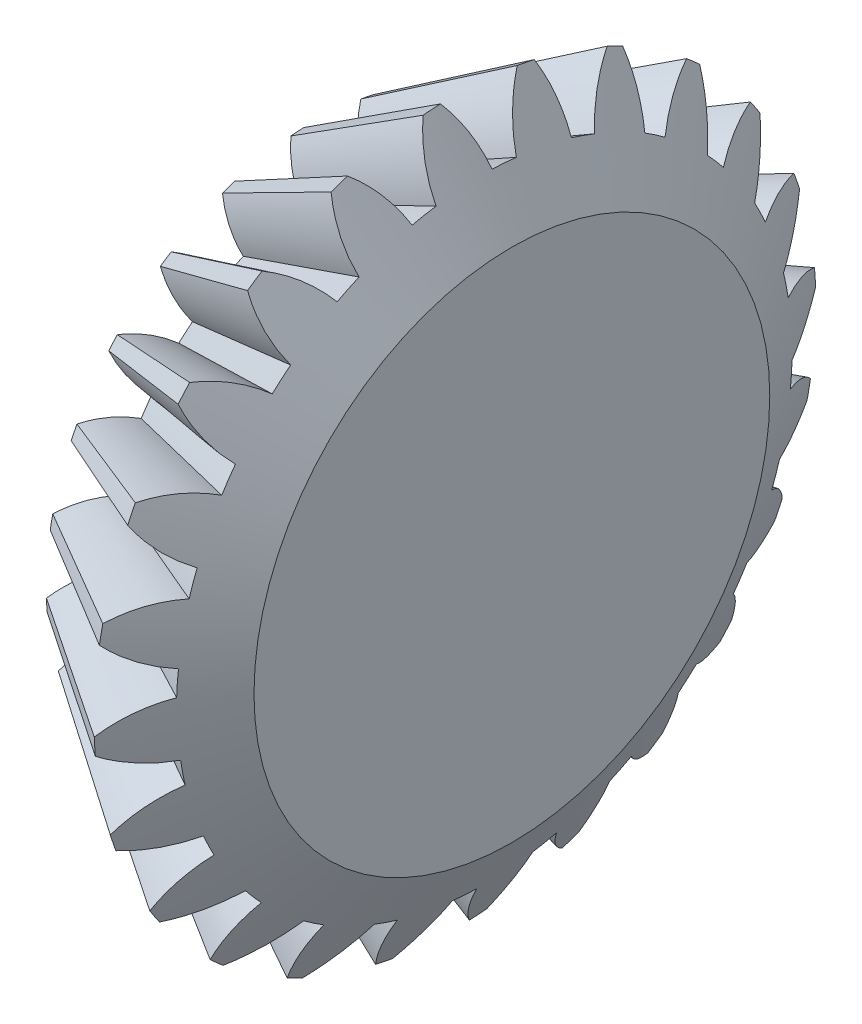
SolidWorks part; units mm, degrees
ref_plane "Front Plane" through (0, 0, 0) normal (0, 0, 1) x (1, 0, 0)
ref_plane "Top Plane" through (0, 0, 0) normal (0, 1, 0) x (1, 0, 0)
ref_plane "Right Plane" through (0, 0, 0) normal (1, 0, 0) x (0, 0, -1)
sketch "Sketch1" plane through (0, 0, 0) normal (0, 0, 1) x (1, 0, 0)
  line L0 (0, 0) -> (-11.5, 0) construction
  line L1 (-11.5, 0) -> (0, 6.9) construction
  line L2 (0, 6.9) -> (0, 0) construction
  line L3 (0, 6.9) -> (3.8127, 0) construction
  line L4 (3.8127, 0) -> (0, 0) construction
  line L5 (0, 6.9) -> (-1.6317, 9.853) construction
  line L6 (-11.5, 0) -> (-0.2781, 7.4033) construction
  line L7 (-11.5, 0) -> (0.3337, 6.2961) construction
  line L8 (-0.2781, 7.4033) -> (0.8899, 5.2895)
  line L9 (0.8899, 5.2895) -> (0.8899, 0)
  line L10 (-0.2781, 7.4033) -> (-3.1579, 5.5034)
  line L11 (-3.1579, 5.5034) -> (-2.379, 4.0939)
  line L12 (-2.379, 4.0939) -> (-2.379, 0)
  line L13 (-2.379, 0) -> (0.8899, 0)
  point P14 (-11.5, 0)
  dimension "D1" = 6.9
  dimension "D2" = 11.5
  dimension "D3" = 0.575
  dimension "D4" = 0.69
  dimension "D5" = 1.15
  dimension "D6" = 3.45
  dimension "D7" = 0.67
revolve "Revolve1" add sketch "Sketch1" angle 360 about L0
ref_plane "Plane1" through (2.9209, 1.614, 0) normal (0.8753, 0.4836, 0) x (0, 0, -1)
sketch "Sketch2" plane through (2.9209, 1.614, 0) normal (0.8753, 0.4836, 0) x (0, 0, -1)
  line L0 (0, -0.8607) -> (0.4889, 6.5983) construction
  line L1 (0, 0) -> (0, 5.5619) construction
  line L2 (0, -0.8607) -> (0, 6.0393) construction
  circle A0 centre (0, -0.8607) radius 7.475 construction
  circle A1 centre (0, -0.8607) radius 6.9 construction
  circle A2 centre (0, -0.8607) radius 6.229 construction
  arc A3 (-0.6737, 7.0501) -> (0.1586, 5.3663) centre (-2.5184, 5.0907) cw
  arc A4 (1.7004, 6.8944) -> (0.6555, 5.3338) centre (3.2737, 4.711) ccw
  arc A5 (0.1586, 5.3663) -> (0.6555, 5.3338) centre (0, -0.8607) cw
  arc A6 (1.7004, 6.8944) -> (-0.6737, 7.0501) centre (0, -0.8607) ccw
  ellipse E0 centre (0, 0.1345) end of major axis (-7.4033, 0.1345) minor radius 6.4798 construction
  dimension "D1" = 14.95
  dimension "D2" = 13.8
  dimension "D3" = 12.458
  dimension "D4" = 3.75
  dimension "D6" = 0.249
sketch "Sketch3" plane through (0, 0, 0) normal (0, 0, 1) x (1, 0, 0)
  point P0 (-11.5, 0)
loft "Cut-Loft1" cut profiles "Sketch3", "Sketch2"
pattern_circular "CirPattern1" count 24 over 360 about axis through (-2.379, 0, 0) along (1, 0, 0) of "Cut-Loft1"
